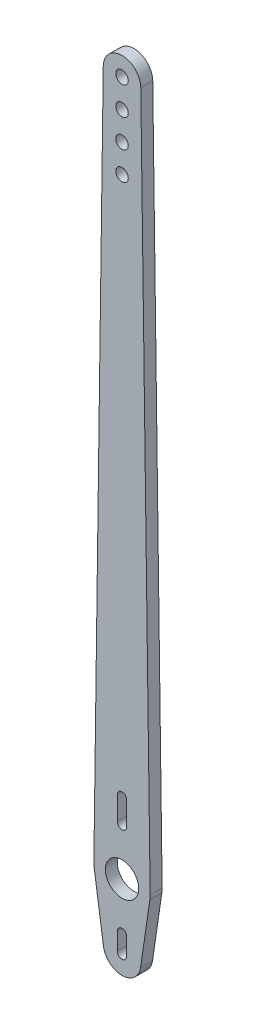
SolidWorks part; units mm, degrees
ref_plane "Front Plane" through (0, 0, 0) normal (0, 0, 1) x (1, 0, 0)
ref_plane "Top Plane" through (0, 0, 0) normal (0, 1, 0) x (1, 0, 0)
ref_plane "Right Plane" through (0, 0, 0) normal (1, 0, 0) x (0, 0, -1)
sketch "Model" plane through (0, 0, 0) normal (0, 0, 1) x (1, 0, 0)
  line L0 (-1, 18.4215) -> (-1, -3.4062) construction
  line L1 (1, 18.4215) -> (1, 5.9161) construction
  line L2 (3.9578, -14.3797) -> (5.9367, -0.8696)
  line L3 (0, 10.1) -> (0, 0) construction
  line L4 (0, -10.1) -> (0, -13.8) construction
  line L5 (-3.9578, -14.3797) -> (-5.9367, -0.8696)
  line L6 (-3.9996, 148.0541) -> (-5.9995, 0.0811)
  line L7 (-7.5978, 10.1) -> (4.5933, 10.1) construction
  line L8 (-1.9126, -10.1) -> (1, -10.1) construction
  line L9 (-3.5953, 15.1) -> (3.0222, 15.1) construction
  line L10 (-2.3019, -13.8) -> (3.0222, -13.8) construction
  line L11 (3.9996, 148.0541) -> (5.9995, 0.0811)
  line L13 (-1, -10.1) -> (-1, -13.8)
  line L14 (1, -10.1) -> (1, -13.8)
  line L15 (-1, 15.1) -> (-1, 10.1)
  line L16 (1, 15.1) -> (1, 10.1)
  line L17 (1, 3.4062) -> (1, -5.9161) construction
  line L18 (1, -10.1) -> (1, -18.7667) construction
  line L19 (-1, -5.9161) -> (-1, -18.7667) construction
  circle A0 centre (0, 0) radius 3.55
  arc A1 (-5.9995, 0.0811) -> (-5.9367, -0.8696) centre (0, 0) ccw
  arc A2 (1, 15.1) -> (-1, 15.1) centre (0, 15.1) ccw
  arc A3 (-1, 10.1) -> (1, 10.1) centre (0, 10.1) ccw
  arc A4 (1, -10.1) -> (-1, -10.1) centre (0, -10.1) ccw
  arc A5 (-1, -13.8) -> (1, -13.8) centre (0, -13.8) ccw
  arc A7 (3.9996, 148.0541) -> (-3.9996, 148.0541) centre (0, 148) ccw
  arc A8 (-3.9578, -14.3797) -> (3.9578, -14.3797) centre (0, -13.8) ccw
  arc A9 (5.9367, -0.8696) -> (5.9995, 0.0811) centre (0, 0) ccw
  circle A14 centre (0, 148) radius 1.33
  circle A15 centre (0, 142) radius 1.33
  circle A16 centre (0, 136) radius 1.33
  circle A17 centre (0, 130) radius 1.33
  point P15 (13.7135, -15.3691)
  point P44 (4, -4.4721)
  point P47 (-4, -4.4721)
  dimension "D1" = 7.1
  dimension "D2" = 12
  dimension "D7" = 2.66
  dimension "D8" = 2.66
  dimension "D20" = 2.66
  dimension "D21" = 2.66
  dimension "D3" = 1
  dimension "D9" = 10.1
  dimension "D10" = 10.1
  dimension "D11" = 3.7
  dimension "D12" = 5
  dimension "D16" = 148
  dimension "D17" = 6
  dimension "D18" = 6
  dimension "D19" = 6
  dimension "D22" = 130
extrude "Boss-Extrude1" add sketch "Model" along normal blind 2.55
